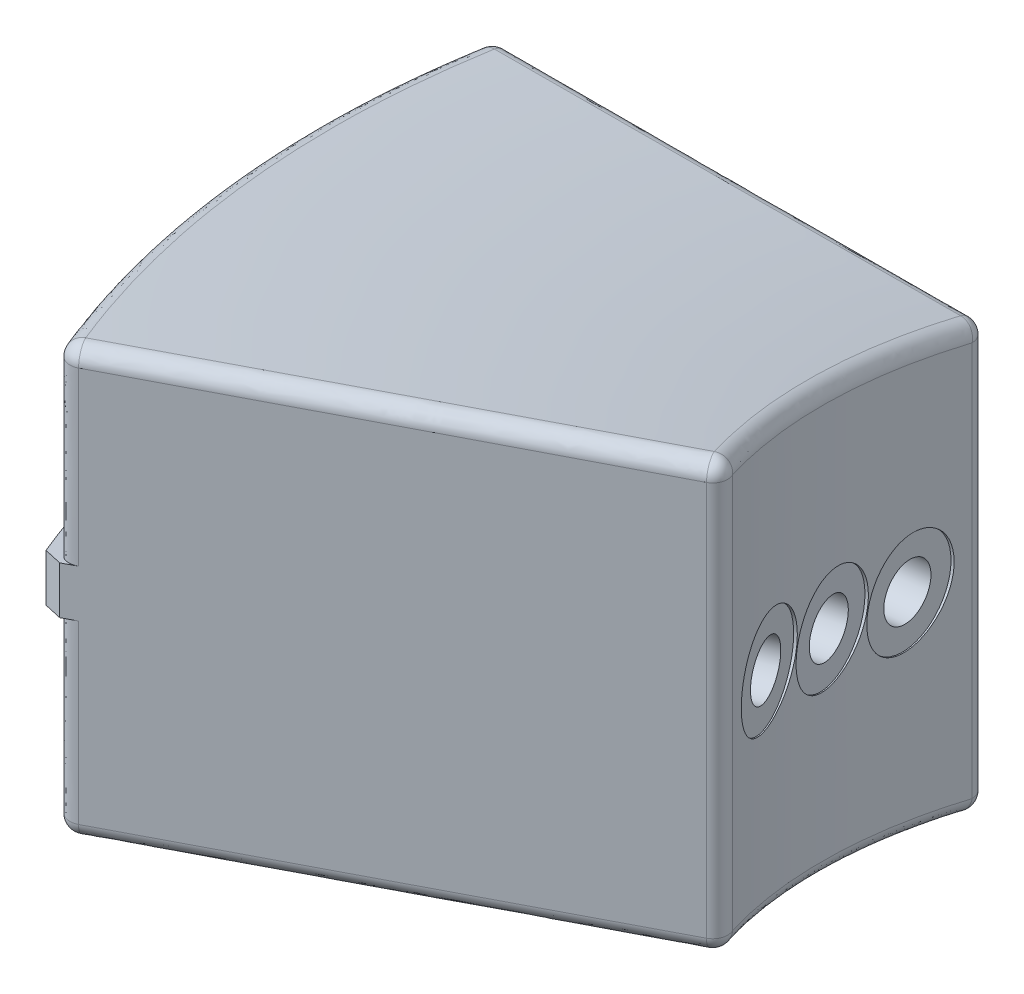
SolidWorks part; units mm, degrees
material "ABS"
ref_plane "Piano frontale" through (0, 0, 0) normal (0, 0, 1) x (1, 0, 0)
ref_plane "Piano superiore" through (0, 0, 0) normal (0, 1, 0) x (1, 0, 0)
ref_plane "Piano destro" through (0, 0, 0) normal (1, 0, 0) x (0, 0, -1)
ref_plane "Piano1" through (0, 21.5, 0) normal (0, 1, 0) x (1, 0, 0)
sketch "Schizzo4" plane through (0, 0, 0) normal (0, 0, 1) x (1, 0, 0)
  line L0 (0, 0) -> (8.4752, 53.5104) construction
  line L1 (-125, 43) -> (-75, 43)
  line L2 (-125, 43) -> (-125, 23.9)
  line L3 (-125, 0) -> (-75, 0)
  line L4 (-75, 43) -> (-75, 0)
  line L5 (-75, 0) -> (0, 0) construction
  line L6 (0, 0) -> (0, 53.441) construction
  line L7 (-125, 19.1) -> (-126.4, 19.1)
  line L8 (-126.4, 19.1) -> (-126.4, 23.9)
  line L9 (-126.4, 23.9) -> (-125, 23.9)
  line L10 (-125, 19.1) -> (-125, 0)
  dimension "D1" = 9
  dimension "D2" = 75
  dimension "D3" = 50
  dimension "D4" = 43
  dimension "D5" = 4.8
  dimension "D6" = 1.4
sketch "Schizzo5" plane through (0, 0, 0) normal (0, 1, 0) x (1, 0, 0)
  line L0 (-125, 0) -> (-75, 0) construction
  circle A0 centre (0, 0) radius 100
  point P5 (-100, 0)
curve "Elica/Spirale2" pitch 120 height 12 turns 0.1
sweep "Sweep1" add profiles "Schizzo4" path "Elica/Spirale2"
sketch "Schizzo10" plane through (0, 0, 0) normal (0, 1, 0) x (1, 0, 0)
  line L0 (0, 0) -> (-39.6115, 0) construction
  line L1 (0, 0) -> (-98.8107, -52.0309) construction
  dimension "D1" = 27.77
sketch "Schizzo6" plane through (0, 21.5, 0) normal (0, 1, 0) x (1, 0, 0)
  circle A0 centre (0, 0) radius 75
  dimension "D1" = 150
curve "Elica/Spirale3" pitch 120 height 9.2567 turns 0.0771
sketch "Schizzo8" plane through (0, 21.5, 0) normal (0, 1, 0) x (1, 0, 0)
  circle A0 centre (0, 0) radius 125
  dimension "D1" = 250
curve "Elica/Spirale4" pitch 120 height 9.2567 turns 0.0771
ref_plane "Piano2" through (0, 0, 0) normal (-0.4659, 0, -0.8848) x (-0.8848, 0, 0.4659)
sketch "Schizzo11" plane through (0, 0, 0) normal (-0.4659, 0, -0.8848) x (-0.8848, 0, 0.4659)
  line L1 (33.1795, -6.1908) -> (160.3476, -6.1908)
  line L2 (33.1795, -6.1908) -> (33.1795, 73.3782)
  line L3 (33.1795, 73.3782) -> (160.3476, 73.3782)
  line L4 (160.3476, -6.1908) -> (160.3476, 73.3782)
extrude "Taglio-Estrusione1" cut sketch "Schizzo11" against normal blind 55
fillet "Raccordo1" radius 1.5 14 edges at (-77.4644, 9.2575, 40.7905) (-99.5006, 52.2575, 52.3941) (-110.6031, 37.9325, 58.2404) (-110.6031, 14.0325, 58.2404)
hole_wizard "Foro lamato per Vite M4 a testa cilindrica piana-1" positions "Schizzo3D1" profile "Schizzo7" counterbore size "M4" standard "ISO"
sketch3d "Schizzo3D1"
  line L0 (0, 0, 0) -> (0, 76.3631, 0) construction
  line L2 (0, 0, 0) -> (-102.1647, 0, 0) construction
  line L4 (0, 0, 0) -> (-14.1534, 0, 1.5838) construction
  line L5 (0, 0, 0) -> (-40.2962, 0, 15.7798) construction
  line L7 (0, 0, 0) -> (-44.2853, 0, 10.9472) construction
  line L9 (-74.5345, 23.6283, 8.3406) -> (0, 23.6283, 0) construction
  line L11 (-72.8086, 26.1283, 17.9981) -> (0, 26.1283, 0) construction
  line L13 (-69.8361, 28.6283, 27.3474) -> (0, 28.6283, 0) construction
  spline S0 degree 3 poles (-75, 21.5, 0) (-75, 22.5275, 4.0349) (-74.3458, 24.5862, 12.1193) (-71.4297, 27.6705, 23.916) (-68.2418, 29.7292, 31.3741) (-66.3619, 30.7567, 34.9443) knots 0 0 0 0 0.333333 0.666667 1 1 1 1 construction
  point P13 (-74.5348, 23.6283, 8.3407)
  point P34 (-72.8085, 26.1283, 17.998)
  point P36 (-69.8363, 28.6283, 27.3475)
  dimension "D1" = 6.385
  dimension "D2" = 15
  dimension "D3" = 7.5
sketch "Schizzo7" plane through (-69.8363, 28.6283, 27.3475) normal (0, 1, 0) x (-0.3646, 0, -0.9312)
  line L0 (0, 0) -> (0, 41.6223)
  line L1 (0, 41.6223) -> (2.7, 40)
  line L2 (2.7, 40) -> (2.7, 0.12)
  line L3 (2.7, 0.12) -> (5, 0.12)
  line L4 (5, 0.12) -> (5, 0)
  line L5 (5, 0) -> (0, 0)
  line L10 (0, 41.6223) -> (-2.7, 40) construction
  line L11 (0, -6.35) -> (0, 107.95) construction
  dimension "Hole Dia." = 5.4
  dimension "Hole Depth" = 40
  dimension "C'Bore Dia." = 10
  dimension "C'Bore Depth" = 0.12
  dimension "Drill Angle" = 118
hole_wizard "Foro lamato per Vite M4 a testa cilindrica piana-2" positions "Schizzo3D2" profile "Schizzo9" counterbore size "M4" standard "ISO"
sketch3d "Schizzo3D2"
  line L0 (0, 0, 0) -> (-125, 0, 0) construction
  line L2 (0, 0, 0) -> (-277.0574, 0, 31.0035) construction
  line L4 (0, 0, 0) -> (0, 60.7615, 0) construction
  line L6 (0, 0, 0) -> (-273.7283, 0, 67.6649) construction
  line L7 (0, 0, 0) -> (-168.3526, 0, 65.9258) construction
  line L9 (-124.2241, 23.6283, 13.901) -> (0, 23.6283, 0) construction
  line L10 (-124.2241, 23.6283, 13.901) -> (-131.1085, 23.6283, 14.6714) construction
  line L11 (-121.3476, 26.1283, 29.9968) -> (0, 26.1283, 0) construction
  line L14 (-121.3476, 26.1283, 29.9968) -> (-131.1438, 26.1283, 32.4184) construction
  line L16 (0, 28.6283, 0) -> (-116.3935, 28.6283, 45.5789) construction
  line L18 (-116.3935, 28.6283, 45.5789) -> (-145.9674, 28.6283, 57.1599) construction
  spline S0 degree 3 poles (-125, 21.5, 0) (-125, 22.5274, 6.7245) (-123.9096, 24.5862, 20.199) (-119.0495, 27.6705, 39.8598) (-113.7362, 29.7292, 52.2904) (-110.6031, 30.7567, 58.2404) knots 0 0 0 0 0.333333 0.666667 1 1 1 1 construction
  point P42 (-125.616, 23.6283, 14.0568)
  point P62 (-122.7065, 26.1283, 30.3327)
  point P64 (-117.6975, 28.6283, 46.0896)
  dimension "D1" = 6.385
  dimension "D2" = 7.5
  dimension "D3" = 15
sketch "Schizzo9" plane through (-117.6975, 28.6283, 46.0896) normal (0, 1, 0) x (0.3646, 0, 0.9312)
  line L0 (0, 0) -> (0, 31.6223)
  line L1 (0, 31.6223) -> (2.7, 30)
  line L2 (2.7, 30) -> (2.7, 3)
  line L3 (2.7, 3) -> (5, 3)
  line L4 (5, 3) -> (5, 0)
  line L5 (5, 0) -> (0, 0)
  line L10 (0, 31.6223) -> (-2.7, 30) construction
  line L11 (0, -6.35) -> (0, 107.95) construction
  dimension "Hole Dia." = 5.4
  dimension "Hole Depth" = 30
  dimension "C'Bore Dia." = 10
  dimension "C'Bore Depth" = 3
  dimension "Drill Angle" = 118
chamfer "Smusso1" distance 1.5 angle 45 2 edges at (-111.8419, 30.7575, 58.8927)
